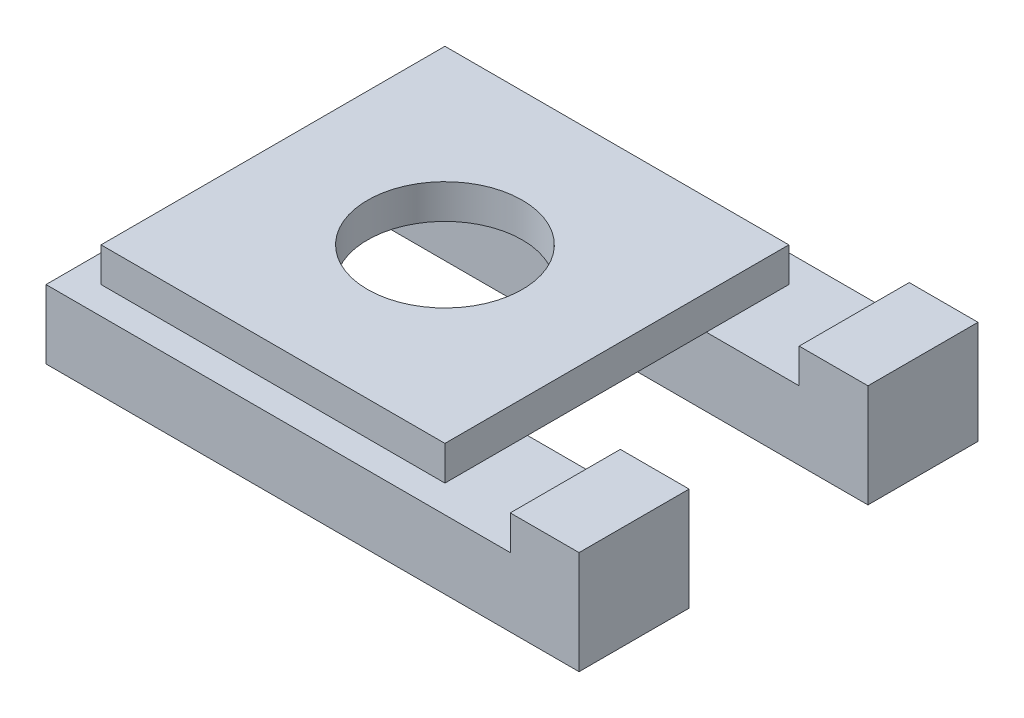
SolidWorks part; units mm, degrees
ref_plane "Front Plane" through (0, 0, 0) normal (0, 0, 1) x (1, 0, 0)
ref_plane "Top Plane" through (0, 0, 0) normal (0, 1, 0) x (1, 0, 0)
ref_plane "Right Plane" through (0, 0, 0) normal (1, 0, 0) x (0, 0, -1)
sketch "Sketch1" plane through (0, 0, 0) normal (0, 1, 0) x (1, 0, 0)
  line L1 (-50, -50) -> (50, -50)
  line L2 (-50, -50) -> (-50, 50)
  line L3 (-50, 50) -> (50, 50)
  line L4 (50, -50) -> (50, 50)
  line L5 (-50, -50) -> (50, 50) construction
  line L6 (-50, 50) -> (50, -50) construction
  circle A0 centre (0, 0) radius 22.5
  point P0 (0, 0)
  dimension "D3" = 45
  dimension "D1" = 100
  dimension "D2" = 100
extrude "Boss-Extrude1" add sketch "Sketch1" along normal blind 10
sketch "Sketch2" plane through (0, 0, 0) normal (0, -1, 0) x (1, 0, 0)
  line L0 (-50, 50) -> (-58, 50)
  line L1 (-58, 50) -> (-58, 58)
  line L2 (77, 58) -> (77, 26)
  line L3 (-58, 58) -> (97, 58)
  line L4 (-58, 58) -> (-58, 26)
  line L5 (-58, 26) -> (97, 26)
  line L6 (97, 58) -> (97, 26)
  line L7 (0, 0) -> (89.8603, 0)
  line L8 (97, -58) -> (97, -26)
  line L9 (77, -58) -> (77, -26)
  line L10 (-58, -26) -> (97, -26)
  line L11 (-58, -58) -> (97, -58)
  line L12 (-58, -58) -> (-58, -26)
  line M1 (50, -50) -> (50, 50)
  line M2 (50, 50) -> (-50, 50)
  line M3 (-50, 50) -> (-50, -50)
  line M4 (-50, -50) -> (50, -50)
  dimension "D1" = 8
  dimension "D2" = 8
  dimension "D3" = 155
  dimension "D4" = 20
  dimension "D5" = 32
extrude "Boss-Extrude4" add sketch "Sketch2" along normal blind 20 contours L4 L5 L0 M3 | L5 L2 L3 L1 L0 M1 M2 | L6 L3 L2 L5 | L5 M3 M1 M2 | L10 M3 M4 M1 | L12 L11 L9 L10 M1 M4 M3 | L9 L11 L8 L10 region at (-54, 0, 38) region at (-54, 0, 51.3874) region at (0, 0, 38) region at (-51.3874, 0, -38) region at (0, 0, -38) region at (87, 0, 42) region at (87, 0, -42)
extrude "Boss-Extrude5" add sketch "Sketch2<5>" against normal blind 10 contours L6 L3 L2 L5 | L9 L11 L8 L10 region at (87, 0, 42) region at (87, 0, -42)
sketch "Sketch2<5>" plane through (0, 0, 0) normal (0, -1, 0) x (1, 0, 0) same geometry as "Sketch2"
